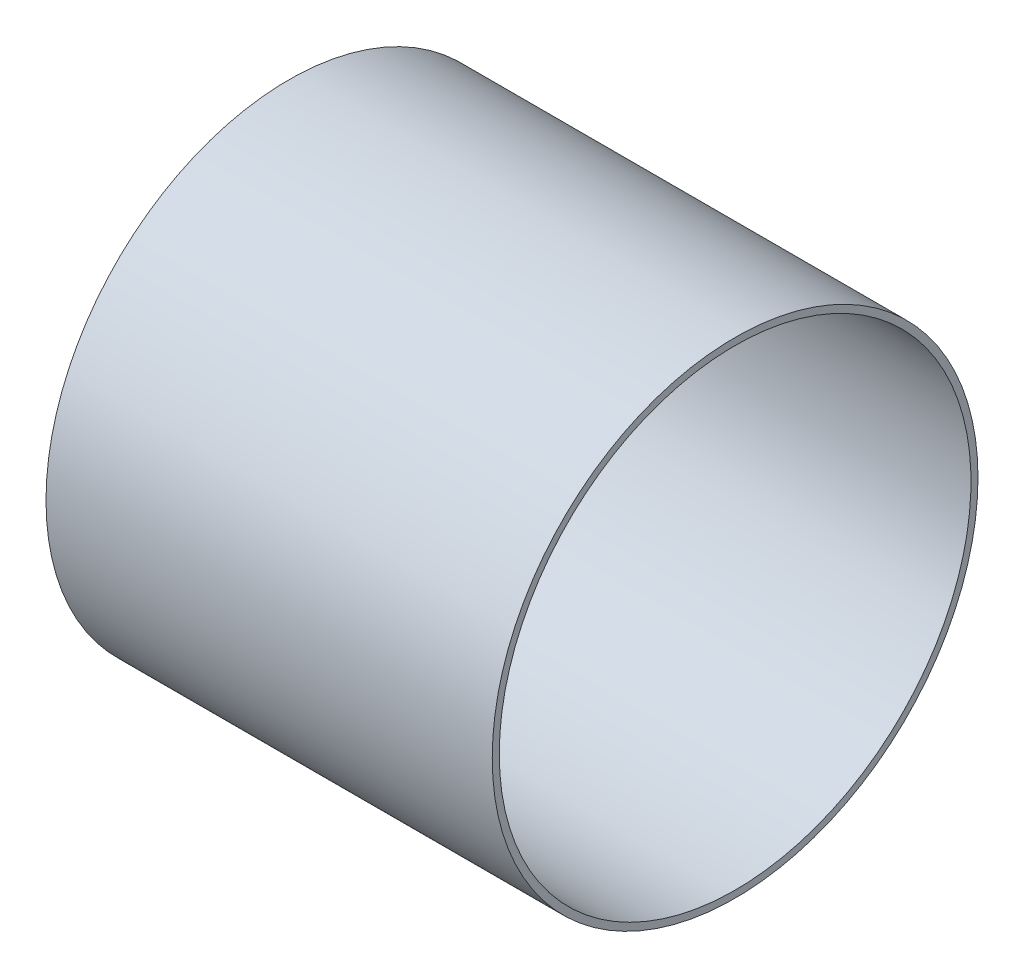
SolidWorks part; units mm, degrees
ref_plane "Front Plane" through (0, 0, 0) normal (0, 0, 1) x (1, 0, 0)
ref_plane "Top Plane" through (0, 0, 0) normal (0, 1, 0) x (1, 0, 0)
ref_plane "Right Plane" through (0, 0, 0) normal (1, 0, 0) x (0, 0, -1)
sketch "Sketch1" plane through (0, 0, 0) normal (1, 0, 0) x (0, 0, -1)
  circle A0 centre (0, 0) radius 57.15
  circle A1 centre (0, 0) radius 55.499
  dimension "D1" = 1.651
  dimension "D2" = 114.3
extrude "Boss-Extrude1" add sketch "Sketch1" along normal blind 105.0009
